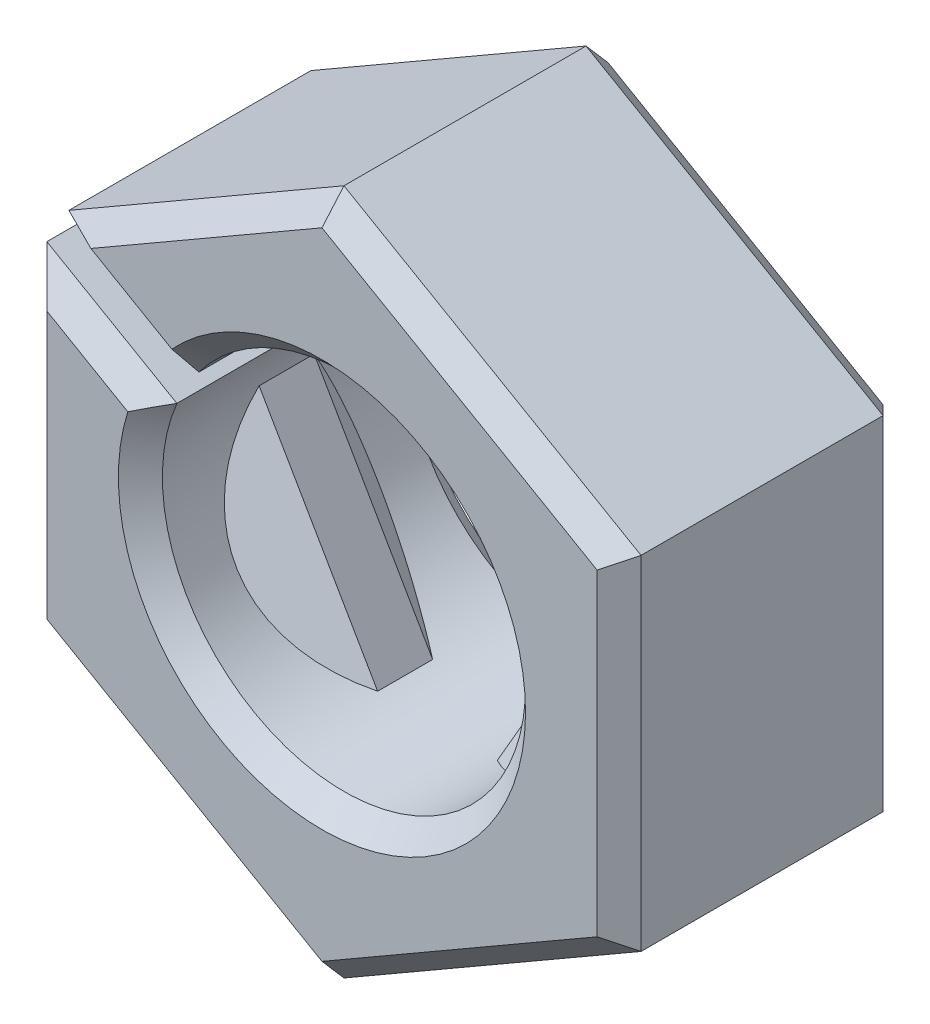
SolidWorks part; units mm, degrees
ref_plane "Front" through (0, 0, 0) normal (0, 0, 1) x (1, 0, 0)
ref_plane "Top" through (0, 0, 0) normal (0, 1, 0) x (1, 0, 0)
ref_plane "Right" through (0, 0, 0) normal (1, 0, 0) x (0, 0, -1)
sketch "Sketch1" plane through (0, 0, 0) normal (0, 0, 1) x (1, 0, 0)
  line L1 (2.7, -1.5588) -> (2.7, 1.5588)
  line L2 (2.7, 1.5588) -> (0, 3.1177)
  line L3 (0, 3.1177) -> (-2.7, 1.5588)
  line L4 (-2.7, 1.5588) -> (-2.7, -1.5588)
  line L5 (-2.7, -1.5588) -> (0, -3.1177)
  line L6 (0, -3.1177) -> (2.7, -1.5588)
  circle A0 centre (0, 0) radius 2.7 construction
  circle A1 centre (0, 0) radius 1.65
  dimension "D1" = 3.3
  dimension "D2" = 5.4
extrude "Boss-Extrude1" add sketch "Sketch1" along normal mid plane 2.6
sketch "Sketch3" plane through (0, 0, 0) normal (1, 0, 0) x (0, 0, -1)
  line L0 (-0.65, 1.65) -> (0.65, 1.65)
  line L1 (1.3, 1.65) -> (-1.3, 1.65) construction
  line L4 (0, 0) -> (0, 1.25) construction
  line L5 (0.65, 1.65) -> (0.25, 1.25)
  line L6 (0.25, 1.25) -> (-0.25, 1.25)
  line L7 (-0.25, 1.25) -> (-0.65, 1.65)
  dimension "D1" = 0.4
  dimension "D2" = 90
  dimension "D3" = 0.5
extrude "Clip" add sketch "Sketch3" along normal up to next and the other way up to next
pattern_circular "Clips x3" count 3 over 360 about axis through (0, 0, 1.3) along (0, 0, 1) of "Clip"
sketch "Sketch4" plane through (0, 0, 0) normal (0, 0, 1) x (1, 0, 0)
  line L0 (-2.7, 1.5588) -> (0, 0)
extrude "Split" cut sketch "Sketch4" against normal through all both and the other way through all thin thin type mid plane wall 0.4
chamfer "Deburs" distance 0.2 angle 45 18 edges at (1.4289, -0.825, -1.3) (2.7, 0, -1.3) (1.35, 2.3383, -1.3) (-1.25, 2.396, -1.3) (-2.7, -0.1155, -1.3) (-1.35, -2.3383, -1.3) (1.35, -2.3383, -1.3) (1.4289, -0.825, 1.3) (-1.35, -2.3383, 1.3) (-2.7, -0.1155, 1.3) (-1.25, 2.396, 1.3) (1.35, 2.3383, 1.3) (2.7, 0, 1.3) (1.35, -2.3383, 1.3) (-1.9092, 1.3332, -1.3) (-2.1092, 0.9868, -1.3) (-1.9092, 1.3332, 1.3) (-2.1092, 0.9868, 1.3)
equation "\"D1@Sketch1\"=\"Clearance Hole Diameter@Box Assy.Assembly\"+.15"
equation "\"D2@Sketch1\"=\"Nut Trap Diameter@Box Assy.Assembly\"-0.3mm"
equation "\"D1@Boss-Extrude1\"=\"Nut Trap Depth@Box Assy.Assembly\""
